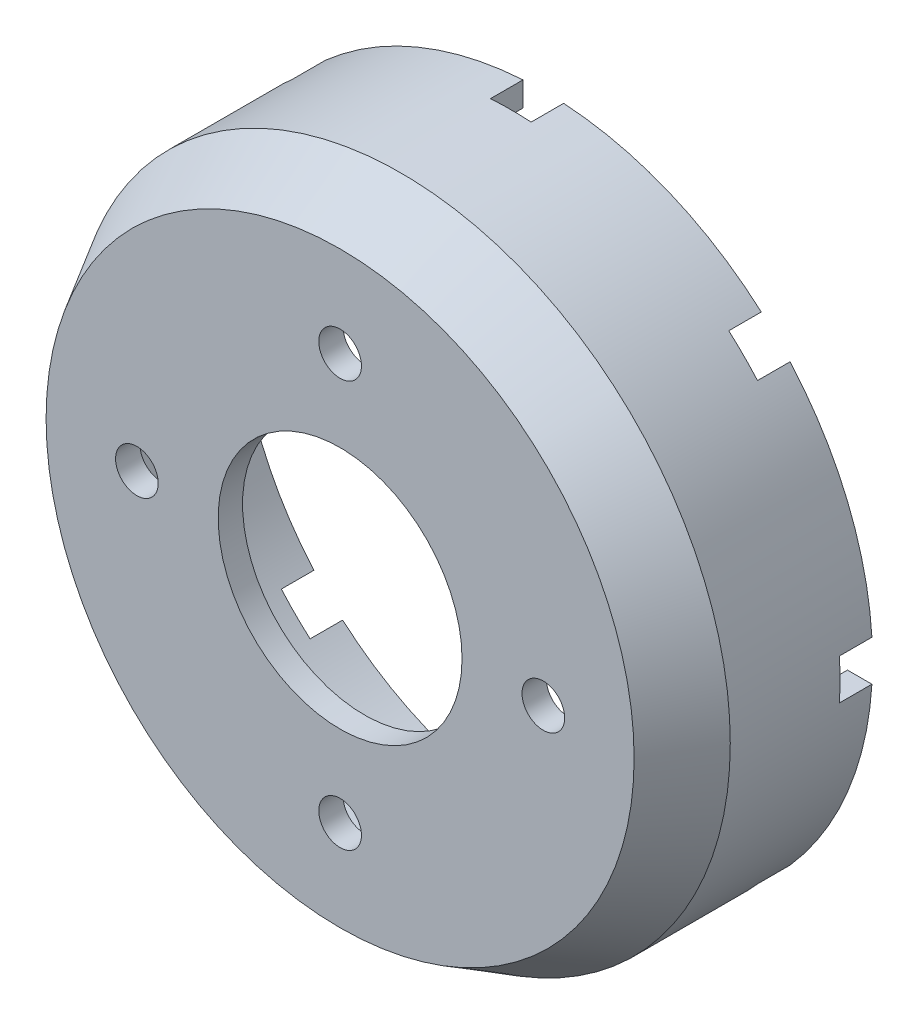
SolidWorks part; units mm, degrees
ref_plane "Płaszczyzna przednia" through (0, 0, 0) normal (0, 0, 1) x (1, 0, 0)
ref_plane "Płaszczyzna górna" through (0, 0, 0) normal (0, 1, 0) x (1, 0, 0)
ref_plane "Płaszczyzna prawa" through (0, 0, 0) normal (1, 0, 0) x (0, 0, -1)
sketch "Szkic1" plane through (0, 0, 0) normal (0, 0, 1) x (1, 0, 0)
  circle A0 centre (0, 0) radius 81
  dimension "D1" = 162
extrude "Dodanie-wyciągnięcie1" add sketch "Szkic1" along normal blind 50
shell "Skorupa1" thickness 6 removed face at (81, 0, 0)
sketch "Szkic2" plane through (0, 0, 0) normal (0, 0, -1) x (-1, 0, 0)
  line L5 (5, 85.8545) -> (5, 69.8212)
  line L6 (-5, 69.8212) -> (-5, 85.8545)
  circle A1 centre (0, 0) radius 86
  circle A2 centre (0, 0) radius 70
  circle A3 centre (0, 0) radius 75 construction
  circle A4 centre (0, 0) radius 81 construction
  circle M10 centre (0, 0) radius 75
  circle M11 centre (0, 0) radius 81
  dimension "D1" = 5
  dimension "D2" = 5
  dimension "D3" = 10
  dimension "D4" = 5
extrude "Wytnij-wyciągnięcie1" cut sketch "Szkic2" against normal blind 8 contours L5 A1 L6 M11 | L6 L5 M10 M11 | A2 L5 L6 M10 region at (0, 83.45, 0) region at (0, 77.9464, 0) region at (0, 72.4424, 0)
pattern_circular "Szyk kołowy1" count 8 over 360 about axis through (0, 0, 50) along (0, 0, -1) of "Wytnij-wyciągnięcie1" reverse direction yes
sketch "Szkic5" plane through (0, 0, 50) normal (0, 0, 1) x (1, 0, 0)
  circle A0 centre (0, 0) radius 30
  circle A1 centre (0, 50) radius 5.25
  circle A2 centre (50, 0) radius 5.25
  circle A3 centre (0, -50) radius 5.25
  circle A4 centre (-50, 0) radius 5.25
  dimension "D1" = 60
  dimension "D3" = 10.5
  dimension "D2" = 50
  dimension "D4" = 4
extrude "Wytnij-wyciągnięcie2" cut sketch "Szkic5" against normal up to surface (6 mm away) up to face at (75, 0, 44)
sketch "Szkic6" plane through (0, 0, 0) normal (0, 0, -1) x (-1, 0, 0)
  line L1 (0, 0) -> (0, 107.389) construction
  line L2 (0, 0) -> (-43.4637, 104.9306) construction
  line L4 (-5, 74.8331) -> (-5, 80.8455) construction
  line L5 (-53.6309, 60.702) -> (-49.3795, 56.4506) construction
  line L6 (-53.6309, 60.702) -> (-49.3795, 56.4506)
  line L7 (-5, 74.8331) -> (-5, 80.8455)
  circle A0 centre (-29.8493, 72.0626) radius 1.5
  circle A1 centre (0, 0) radius 78 construction
  dimension "D1" = 3
  dimension "D2" = 156
  dimension "D3" = 22.5
extrude "Wytnij-wyciągnięcie3" cut sketch "Szkic6" against normal blind 10 contours A0 region at (29.8493, 72.0626, 0)
pattern_circular "Szyk kołowy2" count 8 over 360 about axis through (0, 0, 50) along (0, 0, -1) of "Wytnij-wyciągnięcie3" reverse direction yes
chamfer "Sfazowanie1" distance 15 angle 30 1 edges at (75, 0, 44) first distance on face at (75, 0, 44)
chamfer "Sfazowanie2" distance 15 angle 30 1 edges at (81, 0, 50) first distance on face at (81, 0, 50)
equation "\"D4@Szkic2\"=\"D3@Szkic2\"/2"
equation "\"D2@Szkic6\"=78*2"
